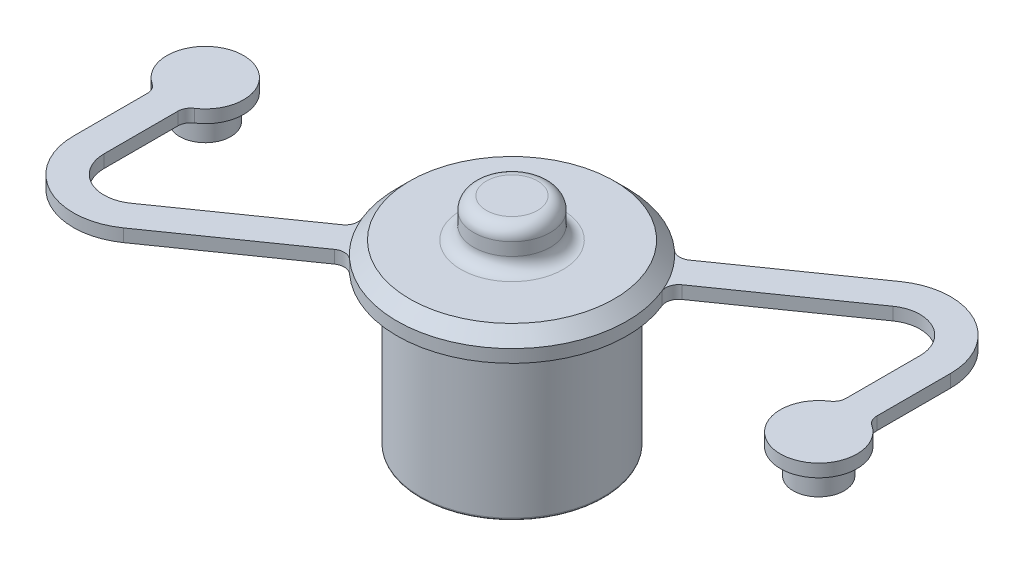
SolidWorks part; units mm, degrees
ref_plane "Front Plane" through (0, 0, 0) normal (0, 0, 1) x (1, 0, 0)
ref_plane "Top Plane" through (0, 0, 0) normal (0, 1, 0) x (1, 0, 0)
ref_plane "Right Plane" through (0, 0, 0) normal (1, 0, 0) x (0, 0, -1)
sketch "Sketch1" plane through (0, 0, 0) normal (0, 1, 0) x (1, 0, 0)
  circle A0 centre (0, 0) radius 3.6
  dimension "D1" = 7.2
extrude "Boss-Extrude1" add sketch "Sketch1" against normal blind 6
sketch "Sketch2" plane through (0, 0, 0) normal (0, 1, 0) x (1, 0, 0)
  circle A0 centre (0, 0) radius 4.5
  dimension "D1" = 9
extrude "Boss-Extrude2" add sketch "Sketch2" along normal blind 1
sketch "Sketch3" plane through (0, 0, 0) normal (0, 1, 0) x (1, 0, 0)
  line L0 (0, 0) -> (8.8528, 6.1988)
  line L1 (12, 4.5605) -> (12, 0)
  arc A0 (8.8528, 6.1988) -> (12, 4.5605) centre (10, 4.5605) cw
  dimension "D1" = 12
  dimension "D3" = 2
  dimension "D2" = 55
extrude "Extrude-Thin1" add sketch "Sketch3" along normal blind 0.5 thin thin type mid plane wall 1.2
sketch "Sketch4" plane through (0, 0, 0) normal (0, 1, 0) x (1, 0, 0)
  line L0 (12.6, 0) -> (11.4, 0) construction
  circle A0 centre (12, 0) radius 1.5
  dimension "D1" = 3
extrude "Boss-Extrude3" add sketch "Sketch4" along normal up to surface (0.5 mm away) up to face at (9.2549, 0.5, -3.5709)
sketch "Sketch5" plane through (0, 0, 0) normal (0, 1, 0) x (1, 0, 0)
  circle A0 centre (12, 0) radius 1
  arc A1 (11.4, 1.3748) -> (12.6, 1.3748) centre (12, 0) ccw construction
  dimension "D1" = 2
extrude "Boss-Extrude4" add sketch "Sketch5" against normal blind 1 contours A0
fillet "Fillet1" radius 0.5 4 edges at (3.9974, 0.25, -2.0666) (3.3091, 0.25, -3.0495) (11.4, 0.25, -1.3748) (12.6, 0.25, -1.3748)
pattern_circular "CirPattern1" count 2 over 360 about axis through (0, -6, 0) along (0, 1, 0) of "Extrude-Thin1", "Boss-Extrude3", "Boss-Extrude4", "Fillet1"
chamfer "Chamfer1" distance 0.5 angle 45 1 edges at (0, 1, 4.5)
sketch "Sketch6" plane through (0, 1, 0) normal (0, 1, 0) x (1, 0, 0)
  circle A0 centre (0, 0) radius 1.5
  dimension "D1" = 3
extrude "Boss-Extrude5" add sketch "Sketch6" along normal blind 1.5
fillet "Fillet2" radius 0.5 1 edges at (0, 2.5, 1.5)
sketch "Sketch7" plane through (0, 0, 0) normal (1, 0, 0) x (0, 0, -1)
  line L0 (0, -6) -> (0, -5.6733)
  line L2 (-3.6, -6) -> (3.6, -6) construction
  line L3 (0, -5.6733) -> (1.7002, -5.6733) construction
  line L4 (0, -6) -> (-3.6, -6)
  arc A0 (0, -5.6733) -> (-3.6, -6) centre (0, -25.6733) ccw
  dimension "D1" = 20
revolve "Cut-Revolve1" cut sketch "Sketch7" angle 360 about L0
fillet "Fillet3" radius 0.1 1 edges at (0, -6, -3.6)
fillet "Fillet4" radius 0.5 1 edges at (0, 1, 1.5)
